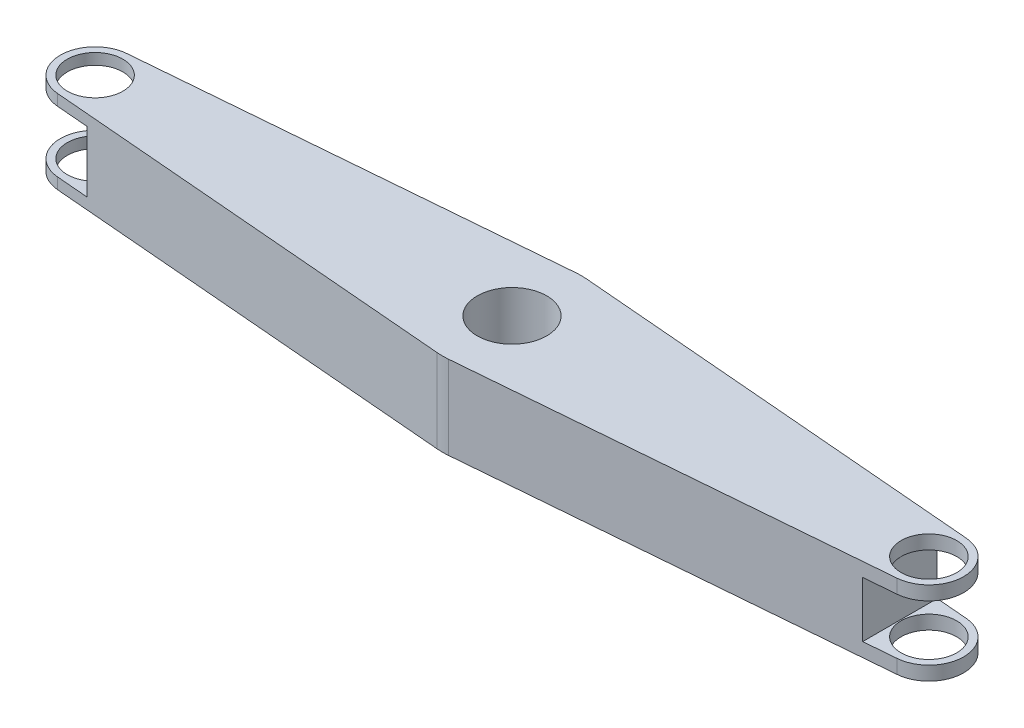
SolidWorks part; units mm, degrees
ref_plane "Alzado" through (0, 0, 0) normal (0, 0, 1) x (1, 0, 0)
ref_plane "Planta" through (0, 0, 0) normal (0, 1, 0) x (1, 0, 0)
ref_plane "Vista lateral" through (0, 0, 0) normal (1, 0, 0) x (0, 0, -1)
sketch "Croquis1" plane through (0, 0, 0) normal (0, 1, 0) x (1, 0, 0)
  line L0 (-150, 0) -> (150, 0) construction
  line L1 (-151.0417, 12.4565) -> (-2.0833, 24.913)
  line L2 (-151.0417, -12.4565) -> (-2.0833, -24.913)
  line L3 (0, 0) -> (0, 42.1122) construction
  line L4 (151.0417, -12.4565) -> (2.0833, -24.913)
  line L5 (151.0417, 12.4565) -> (2.0833, 24.913)
  circle A0 centre (0, 0) radius 12.5
  arc A1 (-2.0833, -24.913) -> (2.0833, -24.913) centre (0, 0) ccw
  arc A2 (-151.0417, 12.4565) -> (-151.0417, -12.4565) centre (-150, 0) ccw
  arc A3 (151.0417, -12.4565) -> (151.0417, 12.4565) centre (150, 0) ccw
  arc A4 (2.0833, 24.913) -> (-2.0833, 24.913) centre (0, 0) ccw
  point P7 (0, 0)
  dimension "D1" = 25
  dimension "D2" = 50
  dimension "D4" = 25
  dimension "D3" = 300
extrude "Saliente-Extruir1" add sketch "Croquis1" along normal mid plane 30
sketch "Croquis2" plane through (0, 0, 0) normal (0, 0, 1) x (1, 0, 0)
  line L0 (-151.0417, 0) -> (151.0417, 0) construction
  line L1 (151.0417, 15) -> (151.0417, -15) construction
  line L2 (162.5, -15) -> (162.5, 15) construction
  line L3 (139.5833, -10) -> (162.5, -10)
  line L4 (139.5833, -10) -> (139.5833, 10)
  line L5 (139.5833, 10) -> (162.5, 10)
  line L6 (162.5, -10) -> (162.5, 10)
  line L7 (139.5833, -10) -> (162.5, 10) construction
  line L8 (139.5833, 10) -> (162.5, -10) construction
  line L9 (-162.5, 15) -> (-162.5, -15) construction
  line L10 (-139.5833, -11) -> (-162.5, -11)
  line L11 (-139.5833, -11) -> (-139.5833, 11)
  line L12 (-139.5833, 11) -> (-162.5, 11)
  line L13 (-162.5, -11) -> (-162.5, 11)
  line L14 (-139.5833, -11) -> (-162.5, 11) construction
  line L15 (-139.5833, 11) -> (-162.5, -11) construction
  point P6 (0, 0)
  dimension "D1" = 20
  dimension "D2" = 22
extrude "Cortar-Extruir1" cut sketch "Croquis2" against normal through all both and the other way through all
sketch "Croquis3" plane through (0, 0, 0) normal (0, 1, 0) x (1, 0, 0)
  circle A0 centre (-150, 0) radius 10
  circle A1 centre (150, 0) radius 10
  dimension "D1" = 20
extrude "Cortar-Extruir2" cut sketch "Croquis3" against normal through all both and the other way through all
